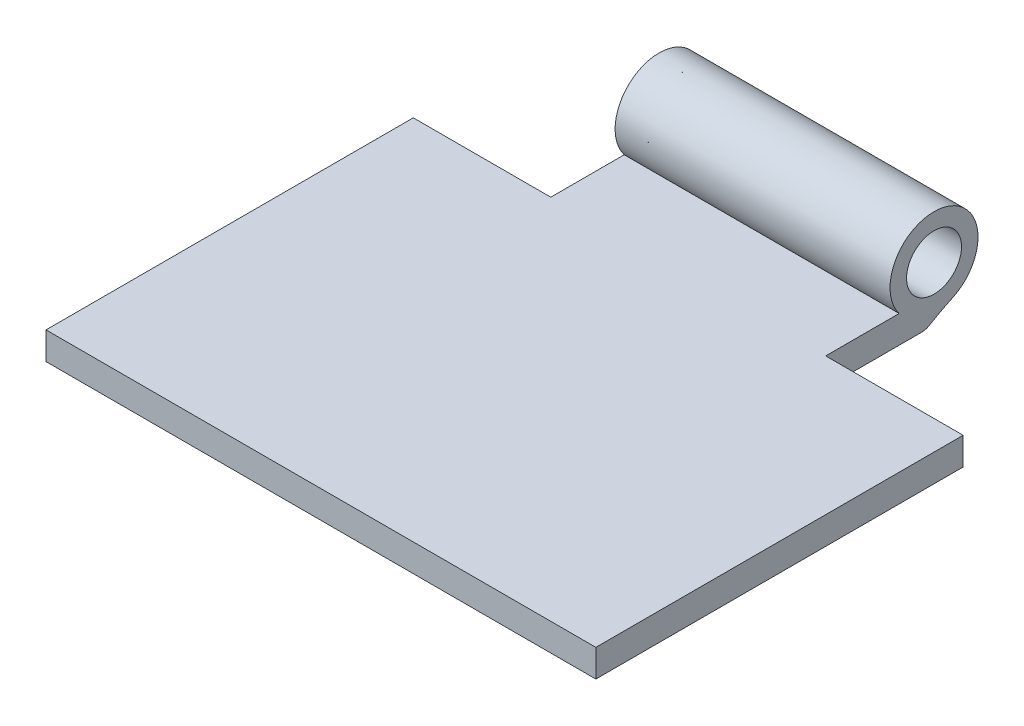
SolidWorks part; units mm, degrees
ref_plane "Front Plane" through (0, 0, 0) normal (0, 0, 1) x (1, 0, 0)
ref_plane "Top Plane" through (0, 0, 0) normal (0, 1, 0) x (1, 0, 0)
ref_plane "Right Plane" through (0, 0, 0) normal (1, 0, 0) x (0, 0, -1)
sketch "Sketch1" plane through (0, 0, 0) normal (0, 1, 0) x (1, 0, 0)
  line L1 (-10, 8.5) -> (10, 8.5)
  line L2 (-10, 8.5) -> (-10, -8.5)
  line L3 (-10, -8.5) -> (10, -8.5)
  line L4 (10, 8.5) -> (10, -8.5)
  line L5 (-10, 8.5) -> (10, -8.5) construction
  line L6 (-10, -8.5) -> (10, 8.5) construction
  point P0 (0, 0)
extrude "Boss-Extrude1" add sketch "Sketch1" along normal blind 1
sketch "Sketch2" plane through (10, 0, 0) normal (1, 0, 0) x (0, 0, -1)
  circle A0 centre (8.8004, 1.9744) radius 1
  circle A1 centre (8.8004, 1.9744) radius 1.6
extrude "Boss-Extrude2" add sketch "Sketch2" against normal up to vertex (20 mm away) up to point (-10, 1, -8.5)
fillet "Fillet1" radius 10 1 edges at (0, 0.4029, -8.5)
fillet "Fillet2" radius 0.5 1 edges at (0, 0, -8.5)
sketch "Sketch4" plane through (0, 0, 0) normal (0, 1, 0) x (1, 0, 0)
  line L0 (0, -5.2453) -> (0, -0.661) construction
  line L1 (15, 4.8599) -> (15, 16.8599)
  line L2 (5, 16.8599) -> (15, 16.8599)
  line L3 (5, 4.8599) -> (5, 16.8599)
  line L4 (5, 4.8599) -> (15, 4.8599)
  line L7 (-5, 4.8599) -> (-15, 4.8599)
  line L8 (-5, 4.8599) -> (-5, 16.8599)
  line L9 (-5, 16.8599) -> (-15, 16.8599)
  line L10 (-15, 4.8599) -> (-15, 16.8599)
extrude "Cut-Extrude3" cut sketch "Sketch4" along normal through all
